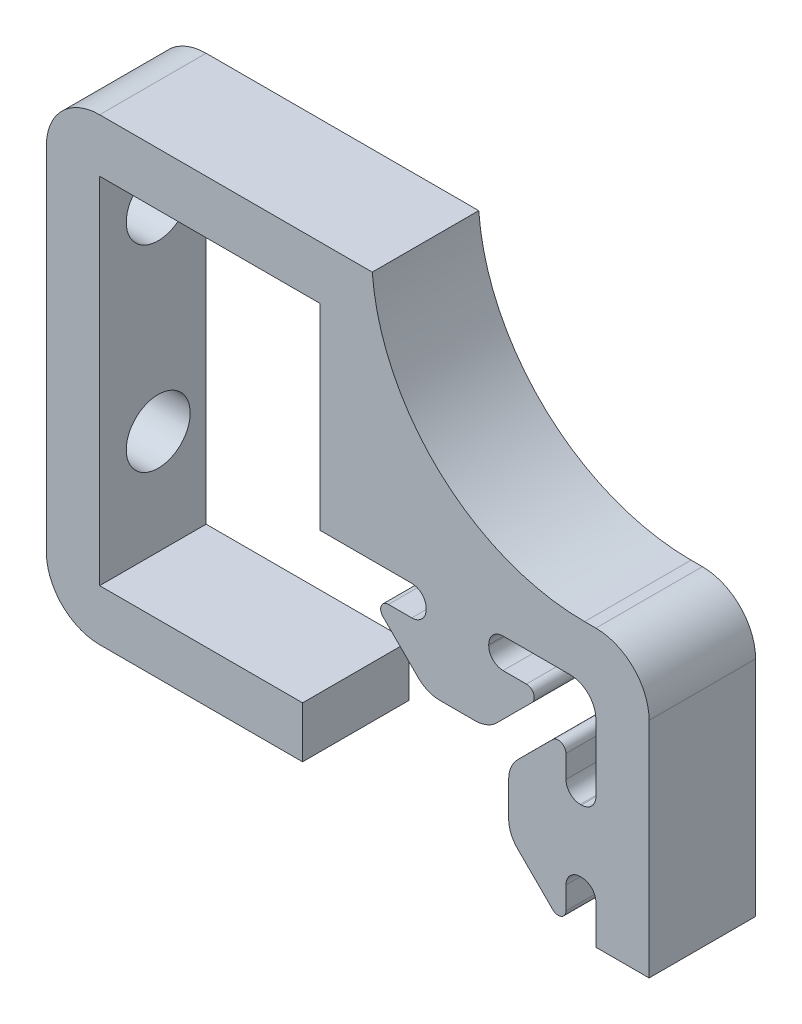
SolidWorks part; units mm, degrees
ref_plane "Front Plane" through (0, 0, 0) normal (0, 0, 1) x (1, 0, 0)
ref_plane "Top Plane" through (0, 0, 0) normal (0, 1, 0) x (1, 0, 0)
ref_plane "Right Plane" through (0, 0, 0) normal (1, 0, 0) x (0, 0, -1)
sketch "Sketch1" plane through (0, 0, 0) normal (0, 0, 1) x (1, 0, 0)
  line L1 (-4.3059, -13) -> (-4.2875, -13)
  line L11 (13, -7.9544) -> (13, -5.3171)
  line L12 (13, -5.3171) -> (13, -4.2875)
  line L13 (11.651, -2.9385) -> (11.5392, -2.9385)
  line L14 (10.1902, -4.2875) -> (10.1902, -6.4021)
  line L15 (8.949, -6.917) -> (5.6529, -3.6284)
  line L16 (4.8085, -1.5932) -> (4.8085, 1.5932)
  line L17 (5.6529, 3.6284) -> (8.949, 6.917)
  line L18 (10.1902, 6.4021) -> (10.1902, 4.2875)
  line L19 (11.5392, 2.9385) -> (11.651, 2.9385)
  line L20 (13, 4.2875) -> (13, 5.3171)
  line L21 (13, 7.9544) -> (13, 10.5918)
  line L22 (10.5918, 13) -> (5.3216, 13)
  line L23 (5.3216, 13) -> (4.2875, 13)
  line L24 (2.9385, 11.651) -> (2.9385, 11.5392)
  line L25 (4.2875, 10.1902) -> (6.4768, 10.1902)
  line L26 (6.9951, 8.9367) -> (3.6864, 5.6355)
  line L27 (1.6558, 4.7958) -> (-1.6558, 4.7958)
  line L28 (-3.6864, 5.6355) -> (-6.9951, 8.9367)
  line L29 (-6.4768, 10.1902) -> (-4.2875, 10.1902)
  line L30 (-2.9385, 11.5392) -> (-2.9385, 11.651)
  line L31 (-4.2875, 13) -> (-4.3059, 13)
  line L32 (-4.3059, 13) -> (-12.9, 13)
  line L33 (-13, 10.5918) -> (-13, 5.3171) construction
  line L34 (-13, 5.3171) -> (-13, 4.2875) construction
  line L35 (-11.651, 2.9385) -> (-11.5392, 2.9385) construction
  line L36 (-10.1902, 4.2875) -> (-10.1902, 6.4021) construction
  line L37 (-8.949, 6.917) -> (-5.6529, 3.6284) construction
  line L38 (-4.8085, 1.5932) -> (-4.8085, -1.5932) construction
  line L39 (-5.6529, -3.6284) -> (-8.949, -6.917) construction
  line L40 (-10.1902, -6.4021) -> (-10.1902, -4.2875) construction
  line L41 (-11.5392, -2.9385) -> (-11.651, -2.9385) construction
  line L43 (18, -7.9544) -> (18, 18)
  line L44 (13, 5.3171) -> (13, 7.9544)
  line L45 (-33.4, 31.3527) -> (-13, 31.3527) construction
  line L46 (-33.4, 31.3527) -> (-33.4, -1.6473) construction
  line L47 (-33.4, -1.6473) -> (-13, -1.6473) construction
  line L48 (-13, 31.3527) -> (-13, -1.6473) construction
  line L53 (-18, -6.6473) -> (-38.6, -6.6473)
  line L54 (-38.6, -6.6473) -> (-38.6, 36.4527)
  line L55 (-38.6, 36.4527) -> (-8, 36.4527)
  line L57 (-12.9, 31.4527) -> (-33.6, 31.4527)
  line L58 (-33.6, 31.4527) -> (-33.6, -1.8473)
  line L59 (-33.6, -1.8473) -> (-14.5421, -1.8473)
  line L61 (18, 18) -> (-8, 18)
  line L62 (-8, 18) -> (-8, 36.4527)
  line L63 (13, -7.9544) -> (18, -7.9544)
  line L64 (-12.9, 31.4527) -> (-12.9, 13)
  line L65 (-4.3059, 13) -> (-10.5918, 13) construction
  line L66 (-18, -6.6473) -> (-14.5421, -6.6473)
  line L67 (-14.5421, -6.6473) -> (-14.5421, -1.8473)
  line L68 (13, -10.5918) -> (13, -5.3171) construction
  line L88 (-7.1797, -8.6452) -> (-3.9523, -5.4237) construction
  line L89 (-1.7093, -4.4958) -> (1.7093, -4.4958) construction
  line L90 (3.9523, -5.4237) -> (7.1797, -8.6452) construction
  line L91 (6.4164, -10.4902) -> (4.2875, -10.4902) construction
  line L92 (3.2385, -11.5392) -> (3.2385, -11.651) construction
  line L93 (4.2875, -12.7) -> (5.3216, -12.7) construction
  line L94 (5.3216, -12.7) -> (10.5918, -12.7) construction
  line L95 (12.7, -10.5918) -> (12.7, -5.3171) construction
  line L96 (12.7, -5.3171) -> (12.7, -4.2875) construction
  line L97 (11.651, -3.2385) -> (11.5392, -3.2385) construction
  line L98 (10.4902, -4.2875) -> (10.4902, -6.4021) construction
  line L99 (8.7371, -7.1294) -> (5.441, -3.8408) construction
  line L100 (4.5085, -1.5932) -> (4.5085, 1.5932) construction
  line L101 (5.441, 3.8408) -> (8.7371, 7.1294) construction
  line L102 (10.4902, 6.4021) -> (10.4902, 4.2875) construction
  line L103 (11.5392, 3.2385) -> (11.651, 3.2385) construction
  line L104 (12.7, 4.2875) -> (12.7, 5.3171) construction
  line L105 (12.7, 5.3171) -> (12.7, 10.5918) construction
  line L106 (10.5918, 12.7) -> (5.3216, 12.7) construction
  line L107 (5.3216, 12.7) -> (4.2875, 12.7) construction
  line L108 (3.2385, 11.651) -> (3.2385, 11.5392) construction
  line L109 (4.2875, 10.4902) -> (6.4768, 10.4902) construction
  line L110 (7.207, 8.7244) -> (3.8983, 5.4232) construction
  line L111 (1.6558, 4.4958) -> (-1.6558, 4.4958) construction
  line L112 (-3.8983, 5.4232) -> (-7.207, 8.7244) construction
  line L113 (-6.4768, 10.4902) -> (-4.2875, 10.4902) construction
  line L114 (-3.2385, 11.5392) -> (-3.2385, 11.651) construction
  line L115 (-4.2875, 12.7) -> (-4.3059, 12.7) construction
  line L116 (-4.3059, 12.7) -> (-10.5918, 12.7) construction
  line L117 (-12.7, 10.5918) -> (-12.7, 5.3171) construction
  line L118 (-12.7, 5.3171) -> (-12.7, 4.2875) construction
  line L119 (-11.651, 3.2385) -> (-11.5392, 3.2385) construction
  line L120 (-10.4902, 4.2875) -> (-10.4902, 6.4021) construction
  line L121 (-8.7371, 7.1294) -> (-5.441, 3.8408) construction
  line L122 (-4.5085, 1.5932) -> (-4.5085, -1.5932) construction
  line L123 (-5.441, -3.8408) -> (-8.7371, -7.1294) construction
  line L124 (-10.4902, -6.4021) -> (-10.4902, -4.2875) construction
  line L125 (-11.5392, -3.2385) -> (-11.651, -3.2385) construction
  line L126 (-12.7, -4.2875) -> (-12.7, -5.3171) construction
  line L127 (-12.7, -5.3171) -> (-12.7, -10.5918) construction
  line L128 (-10.5918, -12.7) -> (-4.3059, -12.7) construction
  line L129 (-4.3059, -12.7) -> (-4.2875, -12.7) construction
  line L130 (-3.2385, -11.651) -> (-3.2385, -11.5392) construction
  line L131 (-4.2875, -10.4902) -> (-6.4164, -10.4902) construction
  line L132 (-13, -4.2875) -> (-13, -5.3171) construction
  line L133 (-13, -5.3171) -> (-13, -10.5918) construction
  line L134 (-10.5918, -13) -> (-4.3059, -13) construction
  line L135 (-4.2875, -10.1902) -> (-6.4164, -10.1902) construction
  line L136 (-6.9677, -8.8575) -> (-3.7403, -5.636) construction
  line L137 (-1.7093, -4.7958) -> (1.7093, -4.7958) construction
  line L138 (3.7403, -5.636) -> (6.9677, -8.8575) construction
  line L139 (6.4164, -10.1902) -> (4.2875, -10.1902) construction
  line L140 (2.9385, -11.5392) -> (2.9385, -11.651) construction
  line L141 (4.2875, -13) -> (5.3216, -13) construction
  line L142 (5.3216, -13) -> (10.5918, -13) construction
  line L143 (-2.9385, -11.651) -> (-2.9385, -11.5392) construction
  line L144 (13, 5.3171) -> (13, 10.5918) construction
  arc A4 (-1.7093, -4.7958) -> (-3.7403, -5.636) centre (-1.7093, -7.6708) ccw
  arc A9 (13, -4.2875) -> (11.651, -2.9385) centre (11.651, -4.2875) ccw
  arc A10 (11.5392, -2.9385) -> (10.1902, -4.2875) centre (11.5392, -4.2875) ccw
  arc A11 (8.949, -6.917) -> (10.1902, -6.4021) centre (9.4628, -6.4021) ccw
  arc A12 (4.8085, -1.5932) -> (5.6529, -3.6284) centre (7.6835, -1.5932) ccw
  arc A13 (5.6529, 3.6284) -> (4.8085, 1.5932) centre (7.6835, 1.5932) ccw
  arc A14 (10.1902, 6.4021) -> (8.949, 6.917) centre (9.4628, 6.4021) ccw
  arc A15 (10.1902, 4.2875) -> (11.5392, 2.9385) centre (11.5392, 4.2875) ccw
  arc A16 (11.651, 2.9385) -> (13, 4.2875) centre (11.651, 4.2875) ccw
  arc A17 (4.2875, 13) -> (2.9385, 11.651) centre (4.2875, 11.651) ccw
  arc A18 (2.9385, 11.5392) -> (4.2875, 10.1902) centre (4.2875, 11.5392) ccw
  arc A19 (6.9951, 8.9367) -> (6.4768, 10.1902) centre (6.4768, 9.4563) ccw
  arc A20 (1.6558, 4.7958) -> (3.6864, 5.6355) centre (1.6558, 7.6708) ccw
  arc A21 (-3.6864, 5.6355) -> (-1.6558, 4.7958) centre (-1.6558, 7.6708) ccw
  arc A22 (-6.4768, 10.1902) -> (-6.9951, 8.9367) centre (-6.4768, 9.4563) ccw
  arc A23 (-4.2875, 10.1902) -> (-2.9385, 11.5392) centre (-4.2875, 11.5392) ccw
  arc A24 (-2.9385, 11.651) -> (-4.2875, 13) centre (-4.2875, 11.651) ccw
  arc A25 (-13, 4.2875) -> (-11.651, 2.9385) centre (-11.651, 4.2875) ccw construction
  arc A26 (-11.5392, 2.9385) -> (-10.1902, 4.2875) centre (-11.5392, 4.2875) ccw construction
  arc A27 (-8.949, 6.917) -> (-10.1902, 6.4021) centre (-9.4628, 6.4021) ccw construction
  arc A28 (-4.8085, 1.5932) -> (-5.6529, 3.6284) centre (-7.6835, 1.5932) ccw construction
  arc A29 (-5.6529, -3.6284) -> (-4.8085, -1.5932) centre (-7.6835, -1.5932) ccw construction
  arc A30 (-10.1902, -6.4021) -> (-8.949, -6.917) centre (-9.4628, -6.4021) ccw construction
  arc A31 (-10.1902, -4.2875) -> (-11.5392, -2.9385) centre (-11.5392, -4.2875) ccw construction
  arc A32 (-11.651, -2.9385) -> (-13, -4.2875) centre (-11.651, -4.2875) ccw construction
  arc A34 (13, 10.5918) -> (10.5628, 12.9998) centre (10.5918, 10.5918) ccw
  arc A35 (-10.5628, 12.9998) -> (-12.9998, 10.5628) centre (-10.5918, 10.5918) ccw construction
  arc A37 (12.9998, 10.5628) -> (10.5628, 12.9998) centre (10.5918, 10.5918) ccw construction
  arc A104 (-7.1797, -8.6452) -> (-6.4164, -10.4902) centre (-6.4164, -9.4098) ccw construction
  arc A105 (-1.7093, -4.4958) -> (-3.9523, -5.4237) centre (-1.7093, -7.6708) ccw construction
  arc A106 (3.9523, -5.4237) -> (1.7093, -4.4958) centre (1.7093, -7.6708) ccw construction
  arc A107 (6.4164, -10.4902) -> (7.1797, -8.6452) centre (6.4164, -9.4098) ccw construction
  arc A108 (4.2875, -10.4902) -> (3.2385, -11.5392) centre (4.2875, -11.5392) ccw construction
  arc A109 (3.2385, -11.651) -> (4.2875, -12.7) centre (4.2875, -11.651) ccw construction
  arc A112 (10.5664, -12.6998) -> (12.6998, -10.5664) centre (10.5918, -10.5918) ccw construction
  arc A115 (12.7, -4.2875) -> (11.651, -3.2385) centre (11.651, -4.2875) ccw construction
  arc A116 (11.5392, -3.2385) -> (10.4902, -4.2875) centre (11.5392, -4.2875) ccw construction
  arc A117 (8.7371, -7.1294) -> (10.4902, -6.4021) centre (9.4628, -6.4021) ccw construction
  arc A118 (4.5085, -1.5932) -> (5.441, -3.8408) centre (7.6835, -1.5932) ccw construction
  arc A119 (5.441, 3.8408) -> (4.5085, 1.5932) centre (7.6835, 1.5932) ccw construction
  arc A120 (10.4902, 6.4021) -> (8.7371, 7.1294) centre (9.4628, 6.4021) ccw construction
  arc A121 (10.4902, 4.2875) -> (11.5392, 3.2385) centre (11.5392, 4.2875) ccw construction
  arc A122 (11.651, 3.2385) -> (12.7, 4.2875) centre (11.651, 4.2875) ccw construction
  arc A125 (12.6998, 10.5664) -> (10.5664, 12.6998) centre (10.5918, 10.5918) ccw construction
  arc A128 (4.2875, 12.7) -> (3.2385, 11.651) centre (4.2875, 11.651) ccw construction
  arc A129 (3.2385, 11.5392) -> (4.2875, 10.4902) centre (4.2875, 11.5392) ccw construction
  arc A130 (7.207, 8.7244) -> (6.4768, 10.4902) centre (6.4768, 9.4563) ccw construction
  arc A131 (1.6558, 4.4958) -> (3.8983, 5.4232) centre (1.6558, 7.6708) ccw construction
  arc A132 (-3.8983, 5.4232) -> (-1.6558, 4.4958) centre (-1.6558, 7.6708) ccw construction
  arc A133 (-6.4768, 10.4902) -> (-7.207, 8.7244) centre (-6.4768, 9.4563) ccw construction
  arc A134 (-4.2875, 10.4902) -> (-3.2385, 11.5392) centre (-4.2875, 11.5392) ccw construction
  arc A135 (-3.2385, 11.651) -> (-4.2875, 12.7) centre (-4.2875, 11.651) ccw construction
  arc A138 (-10.5664, 12.6998) -> (-12.6998, 10.5664) centre (-10.5918, 10.5918) ccw construction
  arc A141 (-12.7, 4.2875) -> (-11.651, 3.2385) centre (-11.651, 4.2875) ccw construction
  arc A142 (-11.5392, 3.2385) -> (-10.4902, 4.2875) centre (-11.5392, 4.2875) ccw construction
  arc A143 (-8.7371, 7.1294) -> (-10.4902, 6.4021) centre (-9.4628, 6.4021) ccw construction
  arc A144 (-4.5085, 1.5932) -> (-5.441, 3.8408) centre (-7.6835, 1.5932) ccw construction
  arc A145 (-5.441, -3.8408) -> (-4.5085, -1.5932) centre (-7.6835, -1.5932) ccw construction
  arc A146 (-10.4902, -6.4021) -> (-8.7371, -7.1294) centre (-9.4628, -6.4021) ccw construction
  arc A147 (-10.4902, -4.2875) -> (-11.5392, -3.2385) centre (-11.5392, -4.2875) ccw construction
  arc A148 (-11.651, -3.2385) -> (-12.7, -4.2875) centre (-11.651, -4.2875) ccw construction
  arc A151 (-12.6998, -10.5664) -> (-10.5918, -12.7) centre (-10.5918, -10.5918) ccw construction
  arc A154 (-4.2875, -12.7) -> (-3.2385, -11.651) centre (-4.2875, -11.651) ccw construction
  arc A155 (-3.2385, -11.5392) -> (-4.2875, -10.4902) centre (-4.2875, -11.5392) ccw construction
  arc A156 (-4.2875, -13) -> (-2.9385, -11.651) centre (-4.2875, -11.651) ccw construction
  arc A157 (-2.9385, -11.5392) -> (-4.2875, -10.1902) centre (-4.2875, -11.5392) ccw construction
  arc A158 (-6.9677, -8.8575) -> (-6.4164, -10.1902) centre (-6.4164, -9.4098) ccw construction
  arc A159 (3.7403, -5.636) -> (1.7093, -4.7958) centre (1.7093, -7.6708) ccw construction
  arc A160 (6.4164, -10.1902) -> (6.9677, -8.8575) centre (6.4164, -9.4098) ccw construction
  arc A161 (4.2875, -10.1902) -> (2.9385, -11.5392) centre (4.2875, -11.5392) ccw construction
  arc A162 (2.9385, -11.651) -> (4.2875, -13) centre (4.2875, -11.651) ccw construction
  dimension "D2" = 33
  dimension "D3" = 20.4
  dimension "D4" = 5
  dimension "D5" = 5
  dimension "D6" = 5
  dimension "D7" = 0.2
  dimension "D9" = 5
  dimension "D10" = 5
  dimension "D11" = 5
  dimension "D12" = 0.2
  dimension "D13" = 0.2
  dimension ".2" = 0.2
  dimension "D1" = 0.3
extrude "Boss-Extrude1" add sketch "Sketch1" along normal blind 10 contours L59 L58 L57 L55 L54 L53 L44 L20 A16 L19 A15 L18 A14 L17 A13 L16 A12 L15 A11 L14 A10 L13 A9 L12 L11 A4 region at (-11.6511, 13.3006, 0)
sketch "Sketch2" plane through (-38.6, 0, 0) normal (-1, 0, 0) x (0, 0, 1)
  line L0 (0, -6.6473) -> (0, 36.4527) construction
  line L3 (4.5, 29.4527) -> (4.5, 26.4527) construction
  line L4 (10, 31.4527) -> (0, 31.4527) construction
  line L5 (4.5, 10.9527) -> (4.5, 4.9527) construction
  line L6 (4.5, 26.4527) -> (4.5, 23.4527) construction
  circle A0 centre (4.5, 26.4527) radius 3
  circle A1 centre (4.5, 7.9527) radius 3
  dimension "D1" = 6
  dimension "D3" = 6
  dimension "D2" = 5
  dimension "D4" = 12.5
  dimension "D5" = 4.5
extrude "Cut-Extrude1" cut sketch "Sketch2" against normal up to next
fillet "Fillet1" radius 20 1 edges at (-8, 18, 5)
fillet "Fillet2" radius 5 3 edges at (-38.6, -6.6473, 5) (18, 18, 5) (-38.6, 36.4527, 5)
